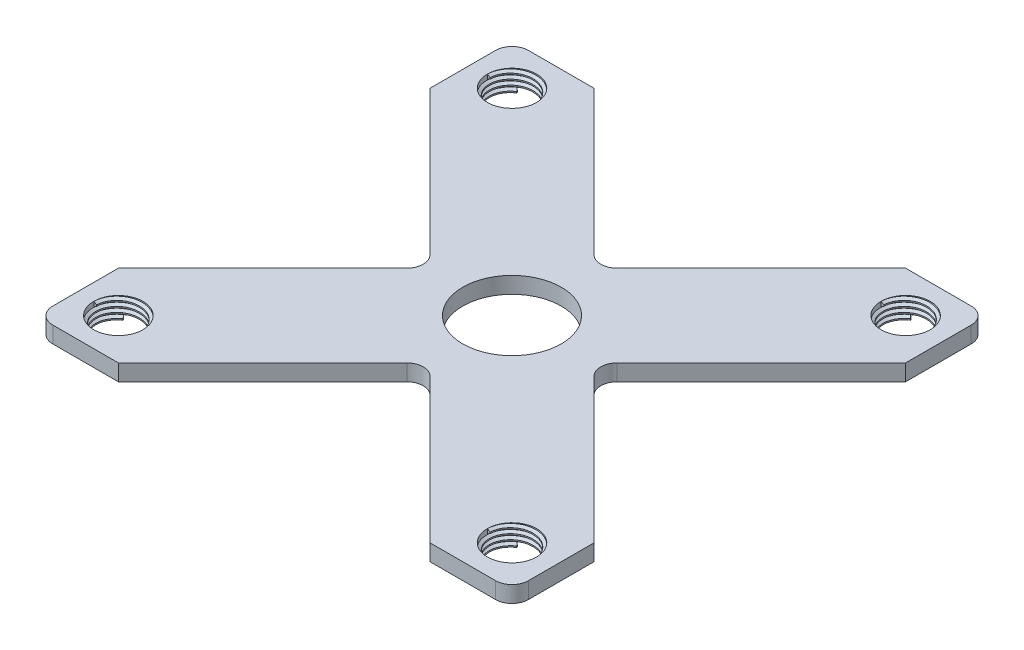
SolidWorks part; units mm, degrees
material "A286 Iron Base Superalloy"
ref_plane "Front Plane" through (0, 0, 0) normal (0, 0, 1) x (1, 0, 0)
ref_plane "Top Plane" through (0, 0, 0) normal (0, 1, 0) x (1, 0, 0)
ref_plane "Right Plane" through (0, 0, 0) normal (1, 0, 0) x (0, 0, -1)
sketch "Sketch1" plane through (0, 0, 0) normal (0, 1, 0) x (1, 0, 0)
  line L0 (0, 0) -> (9.5, 9.5)
  line L1 (9.5, 9.5) -> (19, 0)
  line L2 (24, 5) -> (14.5, 14.5)
  line L3 (14.5, 14.5) -> (24, 24)
  line L4 (19, 29) -> (9.5, 19.5)
  line L5 (9.5, 19.5) -> (0, 29)
  line L6 (-5, 5) -> (4.5, 14.5)
  line L7 (4.5, 14.5) -> (-5, 24)
  line L8 (0, 0) -> (-5, 0)
  line L9 (-5, 0) -> (-5, 5)
  line L10 (-5, 24) -> (-5, 29)
  line L11 (-5, 29) -> (0, 29)
  line L12 (19, 29) -> (24, 29)
  line L13 (24, 29) -> (24, 24)
  line L14 (19, 0) -> (24, 0)
  line L15 (24, 0) -> (24, 5)
  line L16 (0, 0) -> (19, 0) construction
  line L17 (0, 29) -> (19, 29) construction
  line L18 (24, 24) -> (24, 5) construction
  line L19 (-5, 24) -> (-5, 5) construction
  line L20 (4.5, 14.5) -> (14.5, 14.5) construction
  circle A0 centre (9.5, 14.5) radius 3
  dimension "D8" = 6
  dimension "D1" = 5
  dimension "D2" = 19
  dimension "D3" = 19
  dimension "D4" = 45
  dimension "D5" = 45
  dimension "D6" = 45
  dimension "D7" = 45
extrude "Boss-Extrude1" add sketch "Sketch1" along normal blind 1
fillet "Fillet1" radius 1 8 edges at (24, 0.5, 0) (14.5, 0.5, -14.5) (24, 0.5, -29) (9.5, 0.5, -19.5) (-5, 0.5, -29) (4.5, 0.5, -14.5) (9.5, 0.5, -9.5) (-5, 0.5, 0)
sketch "Sketch2" plane through (0, 1, 0) normal (0, 1, 0) x (1, 0, 0)
  line L0 (24, 24) -> (19, 29) construction
  line L1 (0, 29) -> (-5, 24) construction
  line L2 (0, 0) -> (-5, 5) construction
  line L3 (19, 0) -> (24, 5) construction
  circle A0 centre (21.5, 26.5) radius 1.5
  circle A1 centre (-2.5, 26.5) radius 1.5
  circle A2 centre (-2.5, 2.5) radius 1.5
  circle A3 centre (21.5, 2.5) radius 1.5
  dimension "D1" = 3
  dimension "D2" = 3
  dimension "D3" = 3
  dimension "D4" = 3
extrude "Cut-Extrude1" cut sketch "Sketch2" against normal blind 10
thread "Thread1" pitch 0.3175 method extrude profile "Thread Profile1" start angle 0, offset 0, length 1, pitch 0.3175, diameter 3
ref_plane "Plane1" through (-4, 1, -26.5) normal (0, 0, 1) x (-1, 0, 0)
sketch "Thread Profile1" plane through (-4, 1, -26.5) normal (0, 0, 1) x (-1, 0, 0)
  line L0 (0, 0) -> (0, 0.3175) construction
  line L11 (0, 0) -> (0, 0.2778)
  line L12 (0, 0.2778) -> (-0.1719, 0.1786)
  line L13 (-0.1719, 0.1786) -> (-0.1719, 0.0992)
  line L15 (-0.1719, 0.0992) -> (0, 0)
  line L17 (-0.1719, 0.1389) -> (0, 0.1389) construction
  point P2 (0, 0)
  dimension "Pitch" = 0.3175
  dimension "Profile_Angle" = 60
  dimension "Profile_Land" = 0.0794
  dimension "Profile_Height" = 0.1719
thread "Thread2" pitch 0.3175 method extrude profile "Thread Profile2" start angle 0, offset 0, length 1, pitch 0.3175, diameter 3
ref_plane "Plane2" through (-4, 1, -2.5) normal (0, 0, 1) x (-1, 0, 0)
sketch "Thread Profile2" plane through (-4, 1, -2.5) normal (0, 0, 1) x (-1, 0, 0)
  line L0 (0, 0) -> (0, 0.3175) construction
  line L11 (0, 0) -> (0, 0.2778)
  line L12 (0, 0.2778) -> (-0.1719, 0.1786)
  line L13 (-0.1719, 0.1786) -> (-0.1719, 0.0992)
  line L15 (-0.1719, 0.0992) -> (0, 0)
  line L17 (-0.1719, 0.1389) -> (0, 0.1389) construction
  point P2 (0, 0)
  dimension "Pitch" = 0.3175
  dimension "Profile_Angle" = 60
  dimension "Profile_Land" = 0.0794
  dimension "Profile_Height" = 0.1719
thread "Thread3" pitch 0.3175 method extrude profile "Thread Profile3" start angle 0, offset 0, length 1, pitch 0.3175, diameter 3
ref_plane "Plane3" through (20, 1, -2.5) normal (0, 0, 1) x (-1, 0, 0)
sketch "Thread Profile3" plane through (20, 1, -2.5) normal (0, 0, 1) x (-1, 0, 0)
  line L0 (0, 0) -> (0, 0.3175) construction
  line L11 (0, 0) -> (0, 0.2778)
  line L12 (0, 0.2778) -> (-0.1719, 0.1786)
  line L13 (-0.1719, 0.1786) -> (-0.1719, 0.0992)
  line L15 (-0.1719, 0.0992) -> (0, 0)
  line L17 (-0.1719, 0.1389) -> (0, 0.1389) construction
  point P2 (0, 0)
  dimension "Pitch" = 0.3175
  dimension "Profile_Angle" = 60
  dimension "Profile_Land" = 0.0794
  dimension "Profile_Height" = 0.1719
thread "Thread4" pitch 0.3175 method extrude profile "Thread Profile4" start angle 0, offset 0, length 1, pitch 0.3175, diameter 3
ref_plane "Plane4" through (20, 1, -26.5) normal (0, 0, 1) x (-1, 0, 0)
sketch "Thread Profile4" plane through (20, 1, -26.5) normal (0, 0, 1) x (-1, 0, 0)
  line L0 (0, 0) -> (0, 0.3175) construction
  line L11 (0, 0) -> (0, 0.2778)
  line L12 (0, 0.2778) -> (-0.1719, 0.1786)
  line L13 (-0.1719, 0.1786) -> (-0.1719, 0.0992)
  line L15 (-0.1719, 0.0992) -> (0, 0)
  line L17 (-0.1719, 0.1389) -> (0, 0.1389) construction
  point P2 (0, 0)
  dimension "Pitch" = 0.3175
  dimension "Profile_Angle" = 60
  dimension "Profile_Land" = 0.0794
  dimension "Profile_Height" = 0.1719
